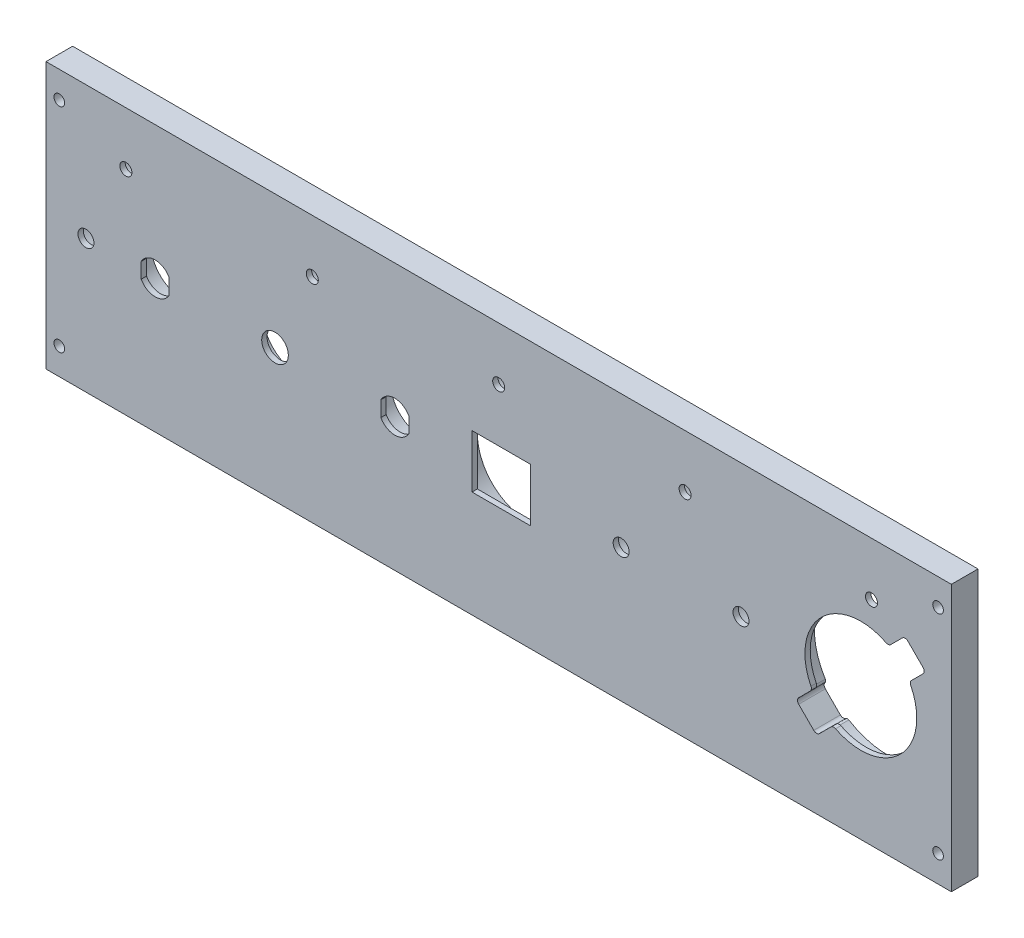
SolidWorks part; units mm, degrees
ref_plane "Plan de face" through (0, 0, 0) normal (0, 0, 1) x (1, 0, 0)
ref_plane "Plan de dessus" through (0, 0, 0) normal (0, 1, 0) x (1, 0, 0)
ref_plane "Plan de droite" through (0, 0, 0) normal (1, 0, 0) x (0, 0, -1)
sketch "Esquisse1" plane through (0, 0, 0) normal (0, 0, 1) x (1, 0, 0)
  line L1 (0, 0) -> (340, 0)
  line L2 (0, 0) -> (0, 100)
  line L3 (0, 100) -> (340, 100)
  line L4 (340, 0) -> (340, 100)
  dimension "D1" = 340
  dimension "D2" = 100
extrude "Boss.-Extru.1" add sketch "Esquisse1" along normal blind 10
sketch "Esquisse2" plane through (0, 0, 10) normal (0, 0, 1) x (1, 0, 0)
  line L0 (0, 50) -> (340, 50) construction
  line L1 (0, 100) -> (0, 0) construction
  line L2 (340, 0) -> (340, 100) construction
  line L3 (160, 40) -> (160, 60)
  line L4 (160, 60) -> (182, 60)
  line L5 (182, 60) -> (182, 40)
  line L6 (160, 40) -> (182, 40)
  line L7 (171, 40) -> (171, 60) construction
  circle A0 centre (15, 50) radius 3
  circle A1 centre (41, 50) radius 6
  circle A2 centre (86, 50) radius 5
  circle A3 centre (131, 50) radius 6
  circle A4 centre (216, 50) radius 3
  circle A5 centre (261, 50) radius 3
  circle A6 centre (306, 50) radius 21
  point P19 (182, 50)
  point P20 (160, 50)
  dimension "D1" = 6
  dimension "D2" = 12
  dimension "D3" = 26
  dimension "D4" = 45
  dimension "D5" = 10
  dimension "D6" = 15
  dimension "D7" = 45
  dimension "D8" = 12
  dimension "D11" = 40
  dimension "D12" = 6
  dimension "D13" = 6
  dimension "D14" = 45
  dimension "D15" = 45
  dimension "D16" = 45
  dimension "D17" = 42
  dimension "D9" = 20
  dimension "D10" = 22
extrude "Enlèv. mat.-Extru.1" cut sketch "Esquisse2" against normal through all both and the other way through all
sketch "Esquisse3" plane through (0, 0, 10) normal (0, 0, 1) x (1, 0, 0)
  line L0 (0, 80) -> (340, 80) construction
  line L1 (0, 100) -> (0, 0) construction
  line L2 (340, 0) -> (340, 100) construction
  line L3 (170, 80) -> (170, 100) construction
  line L4 (340, 100) -> (0, 100) construction
  circle A0 centre (170, 80) radius 2.25
  circle A1 centre (100, 80) radius 2.25
  circle A2 centre (30, 80) radius 2.25
  circle A3 centre (310, 80) radius 2.25
  circle A4 centre (240, 80) radius 2.25
  dimension "D1" = 4.5
  dimension "D2" = 70
  dimension "D3" = 70
  dimension "D4" = 20
extrude "Enlèv. mat.-Extru.2" cut sketch "Esquisse3" against normal through all both and the other way through all
sketch "Esquisse4" plane through (0, 0, 10) normal (0, 0, 1) x (1, 0, 0)
  line L0 (306, 26) -> (306, 50) construction
  line L1 (282, 74) -> (330, 74)
  line L2 (282, 74) -> (282, 26)
  line L3 (282, 26) -> (330, 26)
  line L4 (330, 74) -> (330, 26)
  line L5 (330, 50) -> (306, 50) construction
  dimension "D1" = 48
sketch "Esquisse5" plane through (0, 0, 0) normal (0, 0, -1) x (-1, 0, 0)
  line L7 (-171, 50) -> (-182, 50) construction
  line L8 (-182, 40) -> (-182, 60) construction
  line L9 (-171, 40) -> (-171, 50) construction
  line L10 (-160, 40) -> (-182, 40) construction
  circle A2 centre (-306, 50) radius 27.5
  circle A3 centre (-261, 50) radius 9
  circle A4 centre (-216, 50) radius 7.5
  circle A5 centre (-171, 50) radius 19
  circle A6 centre (-131, 50) radius 11.5
  circle A7 centre (-86, 50) radius 15
  circle A8 centre (-41, 50) radius 11.5
  circle A9 centre (-15, 50) radius 10.5
  dimension "D1" = 55
  dimension "D2" = 21
  dimension "D3" = 23
  dimension "D4" = 30
  dimension "D5" = 23
  dimension "D6" = 38
  dimension "D7" = 15
  dimension "D8" = 18
extrude "Enlèv. mat.-Extru.3" cut sketch "Esquisse5" against normal blind 8
sketch "Esquisse6" plane through (0, 0, 10) normal (0, 0, 1) x (1, 0, 0)
  line L0 (41, 44) -> (41, 56) construction
  line L1 (41, 50) -> (30.5, 50) construction
  line L2 (30.5, 44) -> (30.5, 56)
  line L3 (30.5, 56) -> (35.75, 56)
  line L4 (35.75, 56) -> (35.75, 44)
  line L5 (30.5, 44) -> (35.75, 44)
  line L6 (51.5, 44) -> (46.25, 44)
  line L7 (46.25, 56) -> (46.25, 44)
  line L8 (51.5, 56) -> (46.25, 56)
  line L9 (51.5, 44) -> (51.5, 56)
  line L10 (86, 0) -> (86, 100) construction
  line L11 (0, 0) -> (340, 0) construction
  line L12 (340, 100) -> (0, 100) construction
  line L13 (131, 50) -> (141.5, 50) construction
  line L14 (131, 44) -> (131, 56) construction
  line L15 (120.5, 44) -> (120.5, 56)
  line L16 (120.5, 56) -> (125.75, 56)
  line L17 (125.75, 56) -> (125.75, 44)
  line L18 (120.5, 44) -> (125.75, 44)
  line L19 (141.5, 44) -> (136.25, 44)
  line L20 (136.25, 56) -> (136.25, 44)
  line L21 (141.5, 56) -> (136.25, 56)
  line L22 (141.5, 44) -> (141.5, 56)
  circle A0 centre (41, 50) radius 6 construction
  circle A1 centre (131, 50) radius 6 construction
  point P11 (35.75, 50)
  point P16 (46.25, 50)
  point P35 (125.75, 50)
  point P36 (136.25, 50)
  dimension "D1" = 10.5
  dimension "D2" = 12
extrude "Boss.-Extru.2" add sketch "Esquisse6" against normal up to surface (2 mm away) up to face at (29.5, 50, 8)
sketch "Esquisse7" plane through (0, 0, 10) normal (0, 0, 1) x (1, 0, 0)
  line L0 (50.4747, 41.2759) -> (34.6367, 35.582)
  line L1 (34.6367, 35.582) -> (40.2921, 30.6007)
  line L2 (40.2921, 30.6007) -> (31.9222, 23.6283)
  line L3 (31.9222, 23.6283) -> (47.4522, 29.2114)
  line L4 (47.4522, 29.2114) -> (42.2006, 34.4642)
  line L5 (42.2006, 34.4642) -> (50.4747, 41.2759)
  text T0 "ON" font "Century Gothic" height 5
  text T1 "OFF" font "Century Gothic" height 5
sketch "Esquisse8" plane through (0, 0, 10) normal (0, 0, 1) x (1, 0, 0)
  line L0 (5, 0) -> (5, 100) construction
  line L1 (0, 0) -> (340, 0) construction
  line L2 (340, 100) -> (0, 100) construction
  line L3 (5, 50) -> (-54.2134, 50) construction
  line L4 (0, 100) -> (0, 0) construction
  line L5 (170, 0) -> (170, 100) construction
  line L6 (335, 0) -> (335, 100) construction
  circle A0 centre (5, 90) radius 2
  circle A1 centre (5, 10) radius 2
  circle A2 centre (335, 10) radius 2
  circle A3 centre (335, 90) radius 2
  dimension "D1" = 4
  dimension "D2" = 80
  dimension "D3" = 5
extrude "Enlèv. mat.-Extru.4" cut sketch "Esquisse8" against normal blind 10
sketch "Esquisse9" plane through (0, 0, 0) normal (0, 0, -1) x (-1, 0, 0)
  circle A0 centre (-310, 80) radius 7
  circle A1 centre (-240, 80) radius 7
  circle A2 centre (-170, 80) radius 7
  circle A3 centre (-100, 80) radius 7
  circle A4 centre (-30, 80) radius 7
  dimension "D1" = 14
extrude "Enlèv. mat.-Extru.5" cut sketch "Esquisse9" against normal blind 8
fillet "Congé1" radius 2 2 edges at (315.5823, 75.7765, 4) (303.5061, 77.3867, 4)
sketch "Esquisse10" plane through (0, 0, 8) normal (0, 0, -1) x (-1, 0, 0)
  line L0 (-306, 50) -> (-286.5546, 69.4454) construction
  line L1 (-306, 50) -> (-306, 122.4296) construction
  line L2 (-306, 50) -> (-337.998, 81.998) construction
  line L3 (-314.1317, 65.9099) -> (-321.9099, 58.1317)
  line L5 (-321.9099, 58.1317) -> (-330.3952, 66.617)
  line L6 (-330.3952, 66.617) -> (-322.617, 74.3952)
  line L7 (-314.1317, 65.9099) -> (-322.617, 74.3952)
  line L8 (-290.0901, 41.8683) -> (-281.6048, 33.383)
  line L9 (-289.383, 25.6048) -> (-281.6048, 33.383)
  line L10 (-297.8683, 34.0901) -> (-289.383, 25.6048)
  line L11 (-290.0901, 41.8683) -> (-297.8683, 34.0901)
  arc A0 (-317.5588, 74.9528) -> (-301.3828, 77.1096) centre (-306, 50) ccw construction
  point P13 (-326.5061, 70.5061)
  point P14 (-318.0208, 62.0208)
  point P18 (-293.9792, 37.9792)
  point P19 (-285.4939, 29.4939)
  dimension "D1" = 45
  dimension "D2" = 11
  dimension "D3" = 58
  dimension "D4" = 12
extrude "Enlèv. mat.-Extru.6" cut sketch "Esquisse10" along normal through all both and the other way through all
fillet "Congé2" radius 1.5 8 edges at (289.383, 25.6048, 5) (281.6048, 33.383, 5) (287.78, 39.5582, 9) (295.5582, 31.78, 9) (324.22, 60.4418, 9) (316.4418, 68.22, 9) (322.617, 74.3952, 5) (330.3952, 66.617, 5)
fillet "Congé3" radius 1 4 edges at (328.9416, 65.1635, 4) (321.1635, 72.9416, 4) (283.0584, 34.8365, 4) (290.8365, 27.0584, 4)
sketch "Esquisse11" plane through (0, 0, 10) normal (0, 0, 1) x (1, 0, 0)
  line L0 (306, 29) -> (306, 71) construction
  line L1 (330, 50) -> (282, 50) construction
  line L2 (282, 26) -> (282, 74)
  line L3 (330, 74) -> (282, 74)
  line L4 (330, 26) -> (330, 74)
  line L5 (330, 26) -> (282, 26)
  arc A0 (296.5074, 31.2679) -> (324.7321, 59.4926) centre (306, 50) ccw construction
  arc A2 (315.4926, 68.7321) -> (287.2679, 40.5074) centre (306, 50) ccw construction
  point P7 (306, 50)
  point P9 (306, 74)
  point P17 (306, 26)
  dimension "D1" = 48
  dimension "D2" = 48
